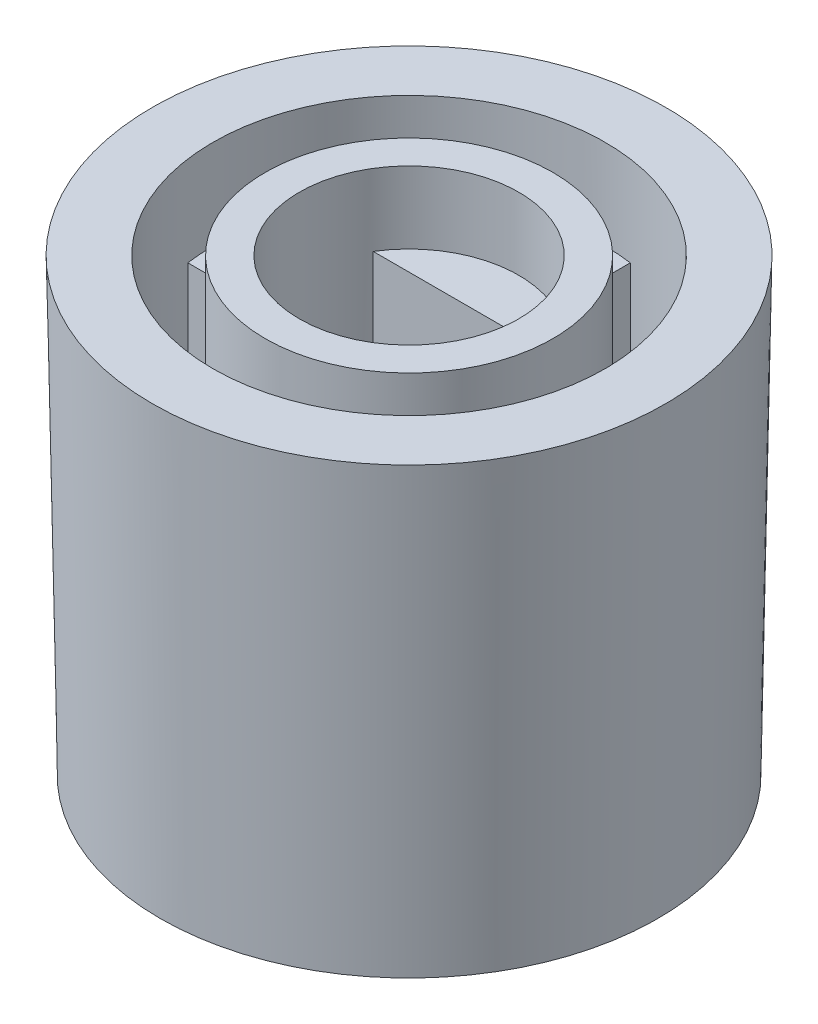
SolidWorks part; units mm, degrees
ref_plane "Front Plane" through (0, 0, 0) normal (0, 0, 1) x (1, 0, 0)
ref_plane "Top Plane" through (0, 0, 0) normal (0, 1, 0) x (1, 0, 0)
ref_plane "Right Plane" through (0, 0, 0) normal (1, 0, 0) x (0, 0, -1)
sketch "Sketch1" plane through (0, 0, 0) normal (0, 1, 0) x (1, 0, 0)
  circle A0 centre (0, 0) radius 6.95
  dimension "D1" = 13.9
extrude "Boss-Extrude1" add sketch "Sketch1" along normal blind 2
sketch "Sketch2" plane through (0, 2, 0) normal (0, 1, 0) x (1, 0, 0)
  circle A0 centre (0, 0) radius 6.95
  circle A1 centre (0, 0) radius 5.45
  dimension "D1" = 13.9
  dimension "D2" = 10.9
extrude "Boss-Extrude2" add sketch "Sketch2" along normal blind 10.5
draft "Draft1" type of draft neutral plane draft angle 1 faces to draft 1 face at (0, 0, 6.95) neutral plane through (0, 2, 0) neutral plane normal (0, 1, 0) reverse direction yes parameters "D1"=1
sketch "Sketch6" plane through (0, 2, 0) normal (0, 1, 0) x (1, 0, 0)
  circle A0 centre (0, 0) radius 4
  dimension "D1" = 8
extrude "Boss-Extrude3" add sketch "Sketch6" along normal blind 10.5
sketch "Sketch5" plane through (0, 12.5, 0) normal (0, 1, 0) x (1, 0, 0)
  line L0 (-2.5966, 1.6) -> (2.5966, 1.6)
  circle A0 centre (0, 0) radius 3.05
  dimension "D1" = 6.1
  dimension "D2" = 1.6
extrude "Cut-Extrude1" cut sketch "Sketch5" against normal blind 9 contours L0 A0 region at (0, 12.5, 0.4883)
sketch "Sketch7" plane through (0, 12.5, 0) normal (0, 1, 0) x (1, 0, 0)
  circle A0 centre (0, 0) radius 3.05
  dimension "D1" = 6.1
extrude "Cut-Extrude2" cut sketch "Sketch7" against normal blind 2
sketch "Sketch8" plane through (0, 2, 0) normal (0, 1, 0) x (1, 0, 0)
  line L1 (-6.116, 0.75) -> (-3.5908, 0.75)
  line L2 (-6.116, 0.75) -> (-6.116, -0.75)
  line L3 (-6.116, -0.75) -> (-3.5908, -0.75)
  line L4 (-3.5908, 0.75) -> (-3.5908, -0.75)
  line L5 (3.6356, 0.75) -> (5.7578, 0.75)
  line L6 (3.6356, 0.75) -> (3.6356, -0.75)
  line L7 (3.6356, -0.75) -> (5.7578, -0.75)
  line L8 (5.7578, 0.75) -> (5.7578, -0.75)
  line L9 (-0.75, 3.5774) -> (0.75, 3.5774)
  line L10 (-0.75, 3.5774) -> (-0.75, 5.9145)
  line L11 (-0.75, 5.9145) -> (0.75, 5.9145)
  line L12 (0.75, 3.5774) -> (0.75, 5.9145)
  line L13 (0.75, -3.4431) -> (-0.75, -3.4431)
  line L14 (0.75, -3.4431) -> (0.75, -6.2011)
  line L15 (0.75, -6.2011) -> (-0.75, -6.2011)
  line L16 (-0.75, -3.4431) -> (-0.75, -6.2011)
  point P16 (-3.5908, 0)
  point P18 (0, 3.5774)
  dimension "D1" = 1.5
extrude "Boss-Extrude4" add sketch "Sketch8" along normal blind 8
